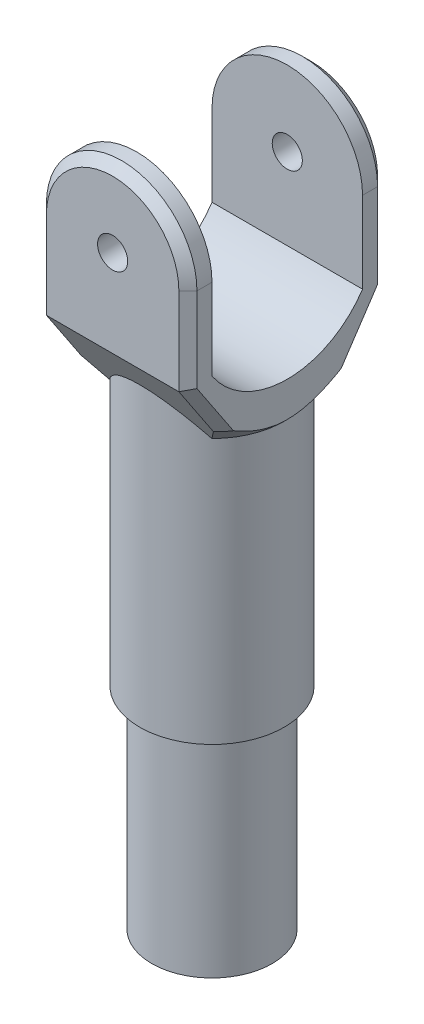
SolidWorks part; units mm, degrees
ref_plane "Front Plane" through (0, 0, 0) normal (0, 0, 1) x (1, 0, 0)
ref_plane "Top Plane" through (0, 0, 0) normal (0, 1, 0) x (1, 0, 0)
ref_plane "Right Plane" through (0, 0, 0) normal (1, 0, 0) x (0, 0, -1)
sketch "Sketch1" plane through (0, 0, 0) normal (0, 1, 0) x (1, 0, 0)
  circle A0 centre (0, 0) radius 50
  dimension "D1" = 100
extrude "Boss-Extrude1" add sketch "Sketch1" along normal blind 175
sketch "Sketch4" plane through (0, 175, 0) normal (0, 1, 0) x (1, 0, 0)
  circle A0 centre (0, 0) radius 60
  circle A1 centre (0, 0) radius 50 construction
  dimension "D1" = 10
extrude "Boss-Extrude3" add sketch "Sketch4" along normal blind 250
sketch "Sketch5" plane through (0, 0, 0) normal (1, 0, 0) x (0, 0, -1)
  line L0 (-62.5, 425) -> (62.5, 425)
  line L1 (62.5, 425) -> (82.5, 455)
  line L2 (82.5, 455) -> (82.5, 590)
  line L3 (82.5, 590) -> (62.5, 590)
  line L4 (62.5, 590) -> (62.5, 460)
  line L5 (62.5, 460) -> (-62.5, 460)
  line L6 (-62.5, 460) -> (-62.5, 590)
  line L7 (-62.5, 590) -> (-82.5, 590)
  line L8 (-82.5, 590) -> (-82.5, 455)
  line L9 (-82.5, 455) -> (-62.5, 425)
  line L10 (60, 425) -> (-60, 425) construction
  line L11 (-82.5, 455) -> (-62.5, 455) construction
  line L12 (-62.5, 455) -> (-62.5, 425) construction
  line L13 (62.5, 425) -> (62.5, 455) construction
  line L14 (62.5, 455) -> (82.5, 455) construction
  line L15 (0, 425) -> (0, 460) construction
  point P10 (0, 425)
  point P17 (60, 454.2002)
  dimension "D1" = 30
  dimension "D2" = 20
  dimension "D3" = 125
  dimension "D4" = 130
  dimension "D5" = 20
  dimension "D6" = 35
extrude "Boss-Extrude4" add sketch "Sketch5" along normal mid plane 125
sketch "Sketch6" plane through (0, 0, 82.5) normal (0, 0, 1) x (1, 0, 0)
  line L0 (-62.5, 590) -> (-62.5, 455) construction
  line L1 (62.5, 590) -> (-62.5, 590) construction
  line L2 (62.5, 590) -> (62.5, 455) construction
  line L3 (-62.5, 527.5) -> (-67.5, 527.5)
  line L4 (-67.5, 527.5) -> (-67.5, 595)
  line L5 (-67.5, 595) -> (67.5, 595)
  line L6 (67.5, 595) -> (67.5, 527.5)
  line L7 (67.5, 527.5) -> (62.5, 527.5)
  arc A0 (62.5, 527.5) -> (-62.5, 527.5) centre (0, 527.5) ccw
  circle A1 centre (0, 527.5) radius 12.5
  arc A2 (-62.5, 527.5) -> (62.5, 527.5) centre (0, 527.5) ccw construction
  dimension "D1" = 25
  dimension "D2" = 5
  dimension "D3" = 5
extrude "Cut-Extrude2" cut sketch "Sketch6" against normal through all both and the other way through all
chamfer "Chamfer2" distance 30 angle 45 1 edges at (0, 425, 60)
chamfer "Chamfer3" distance 7.5 angle 45 10 edges at (-62.5, 438.4866, 71.4911) (-62.5, 438.4866, -71.4911) (62.5, 438.4866, -71.4911) (62.5, 438.4866, 71.4911) (-62.5, 491.25, -82.5) (62.5, 491.25, -82.5) (0, 590, -82.5)
sketch "Sketch7" plane through (-62.5, 0, 0) normal (-1, 0, 0) x (0, 0, 1)
  line L0 (0, 460) -> (0, 501.4578) construction
  line L1 (-62.5, 460) -> (62.5, 460) construction
  line L3 (-62.5, 460) -> (62.5, 460)
  arc A0 (-62.5, 460) -> (62.5, 460) centre (0, 501.4578) ccw
  dimension "D1" = 75
extrude "Cut-Extrude3" cut sketch "Sketch7" against normal through all both and the other way through all
